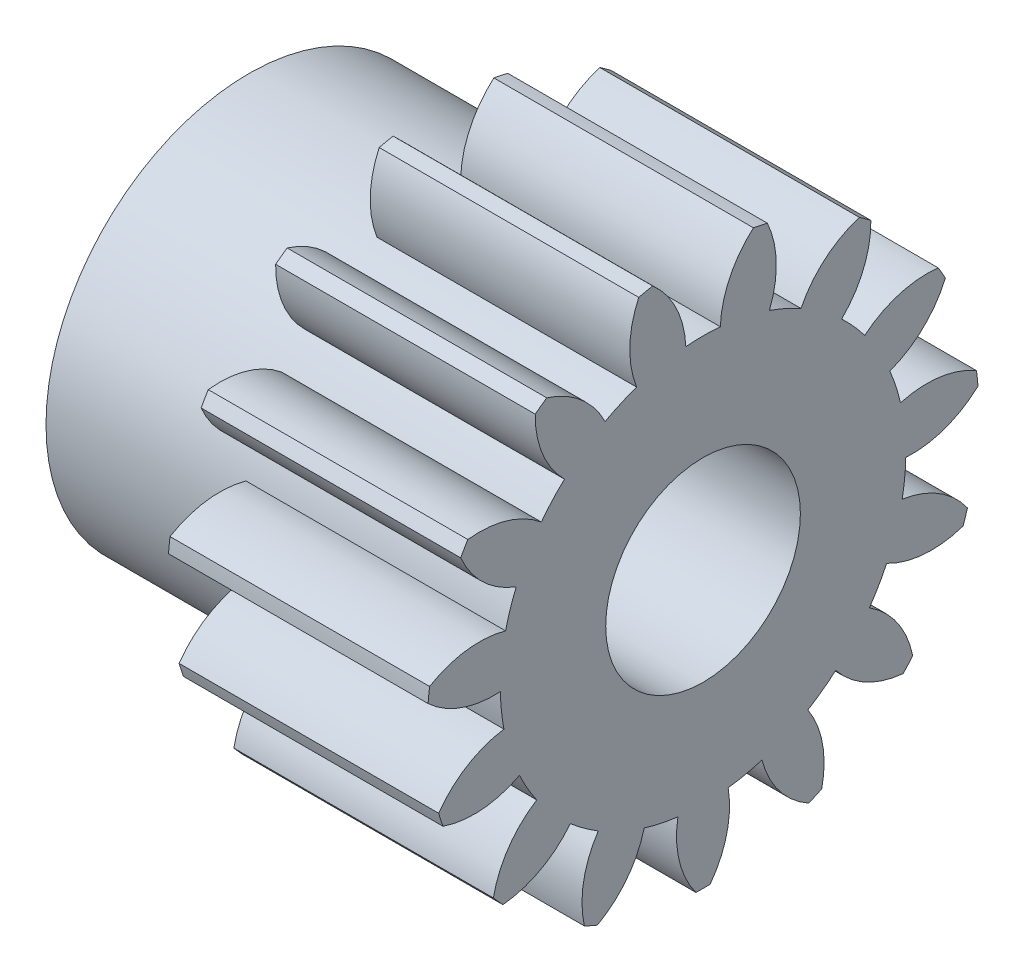
SolidWorks part; units mm, degrees
ref_plane "Plane1" through (0, 0, 0) normal (0, 0, 1) x (1, 0, 0)
ref_plane "Plane2" through (0, 0, 0) normal (0, 1, 0) x (1, 0, 0)
ref_plane "Plane3" through (0, 0, 0) normal (1, 0, 0) x (0, 0, -1)
sketch "HoldingSke" plane through (0, 0, 0) normal (0, 1, 0) x (1, 0, 0)
  line L0 (0, 0) -> (0.9659, -0.2588)
  line L1 (-15, 0) -> (100, 0) construction
  line L2 (0, 0) -> (-2.1039, 2.3779)
  line L3 (0, 0) -> (-11.863, 4.5341)
  line L4 (0, 0) -> (8.3417, 2.2352)
  line L5 (0, 0) -> (-10.3065, -3.844)
  line L6 (0, 0) -> (-6.6317, -4.4744)
  line L7 (-2.1039, 2.3779) -> (0.2639, 13.1202)
  line L8 (-76.2, 54.61) -> (-75.2, 54.61)
  line L9 (-71.009, 38.7566) -> (-53.1078, 45.2721)
  line L10 (-76.2, 71.12) -> (104.1128, 71.12)
  line L11 (0, 0) -> (-8, 0)
  line L12 (-76.2, 101.6) -> (-76.162, 101.6)
  line L13 (24.9733, 27.94) -> (52.9518, 28.4284)
  line L14 (24.9733, 27.94) -> (24.9743, 27.94)
  line L15 (24.9733, 27.94) -> (100.4006, 29.5858)
  line L16 (-63.627, -1) -> (-12.827, -1)
  circle A0 centre (0, 0) radius 3
  circle A1 centre (0, 0) radius 6.249
  circle A2 centre (0, 0) radius 6.5
  circle A3 centre (0, 0) radius 3
  dimension "Num_teeth" = 15
  dimension "Pitch_radius" = 180.3128
  dimension "Width" = 8
  dimension "Thickness" = 8
sketch "BasProSke" plane through (0, 0, 0) normal (0, 1, 0) x (1, 0, 0)
  line L0 (-10, 0) -> (60, 0) construction
  line L1 (0, 0) -> (0, 8.5)
  line L2 (0, 0) -> (8, 0)
  line L3 (8, 0) -> (8, 8.5)
  line L4 (8, 8.5) -> (0, 8.5)
  dimension "Thickness" = 8
  dimension "Diameter" = 17
revolve "Base-Revolve" add sketch "BasProSke" angle 360 about L0
sketch "TooCutSke" plane through (0, 0, 0) normal (1, 0, 0) x (0, 0, -1)
  line L1 (0, 0) -> (0, 107) construction
  line L2 (0, 0) -> (-0.8504, 7.4516) construction
  line L3 (0, 0) -> (-3.1044, 14.6049) construction
  line L4 (-0.8504, 7.4516) -> (-1.5522, 7.3025) construction
  arc A0 (0.5316, 6.2263) -> (-0.5316, 6.2263) centre (0, 0) ccw
  arc A1 (1.5766, 8.3784) -> (-1.5766, 8.3784) centre (0, 0) ccw
  circle A2 centre (0, 0) radius 7.5 construction
  circle A3 centre (0, 0) radius 7.0477 construction
  arc A4 (-0.5316, 6.2263) -> (-1.5766, 8.3784) centre (-3.5289, 6.1005) ccw
  arc A5 (1.5766, 8.3784) -> (0.5316, 6.2263) centre (3.5289, 6.1005) ccw
extrude "ToothCut" cut sketch "TooCutSke" along normal through all
fillet "Breaks" [suppressed] radius 0.02 tangent propagation no
fillet "RootFillets" [suppressed] radius 0.251
pattern_circular "TeethCuts" count 15 every 24 about axis through (-10, 0, 0) along (1, 0, 0) of "ToothCut", "RootFillets", "Breaks"
sketch "HubNeaOneSke" plane through (0, 0, 0) normal (-1, 0, 0) x (0, 0, 1)
  circle A0 centre (0, 0) radius 6.249
  dimension "Diameter" = 12.498
extrude "HubNearOne" add sketch "HubNeaOneSke" along normal blind 3.0002
ref_plane "FarPln" through (8, 0, 0) normal (1, 0, 0) x (0, 0, -1)
sketch "BorSke" plane through (0, 0, 0) normal (1, 0, 0) x (0, 0, -1)
  circle A0 centre (0, 0) radius 3
  dimension "Diameter" = 6
extrude "Bore" cut sketch "BorSke" along normal mid plane 22.0003
other "Move Face1" face at (-3.0002, 0, 3) offset 3 parameters "D1"=3
equation "' \"Module@HoldingSke\" = 6.35"
equation "' \"Num_teeth@HoldingSke\" = 12"
equation "' \"Ap@HoldingSke\" =  20"
equation "' \"Ap@HoldingSke\" = 20"
equation "' \"Width@HoldingSke\" = 0.5 * 25.4"
equation "' \"Hub_dia@HoldingSke\"= 1 * 25.4"
equation "' \"Hub_dia@HoldingSke\" = 1 * 25.4"
equation "' \"Overall_len@HoldingSke\" = 1.0 * 25.4"
equation "' \"Bore@HoldingSke\" = 0.75 * 25.4"
equation "' \"T_dim@HoldingSke\" = 0.1 * 25.4"
equation "' \"Width@KeySke\" = 0.25 * 25.4"
equation "' \"Show_teeth@HoldingSke\" = 13"
equation "' \"Backlash@HoldingSke\" = 0.009 * 25.4"
equation "' \"Addendum_fac@HoldingSke\" = 1.0"
equation "' \"Dedendum_fac@HoldingSke\" = 1.25"
equation "' \"Dedendum_add@HoldingSke\" = 0.00005 * 25.4"
equation "' \"Clearance_fac@HoldingSke\" = 0.25"
equation "\"Pitch@HoldingSke\" = 1 / \"Module@HoldingSke\""
equation "\"Overcut_dia@TooCutSke\" = (\"Num_teeth@HoldingSke\" + 2 * \"Addendum_fac@HoldingSke\") / \"Pitch@HoldingSke\" + 0.002 * 25.4"
equation "\"Pitch_dia@TooCutSke\" = \"Num_teeth@HoldingSke\" / \"Pitch@HoldingSke\""
equation "\"Base_dia@TooCutSke\" = \"Num_teeth@HoldingSke\" / \"Pitch@HoldingSke\" * cos((\"Ap@HoldingSke\"  * 3.14159265 / 180))"
equation "\"Root_dia@TooCutSke\" = (\"Num_teeth@HoldingSke\" + 2) / \"Pitch@HoldingSke\" - 2 * (\"Addendum_fac@HoldingSke\" + \"Dedendum_fac@HoldingSke\") / \"Pitch@HoldingSke\" - \"Dedendum_add@HoldingSke\" * 2"
equation "\"Half_ang@TooCutSke\" = 180 / \"Num_teeth@HoldingSke\""
equation "\"Half_CT@TooCutSke\" = \"Num_teeth@HoldingSke\" / \"Pitch@HoldingSke\" * sin((3.14159265 / 2 / \"Num_teeth@HoldingSke\")) / 2 - 7 * \"Backlash@HoldingSke\" / 4"
equation "\"Flank_rad@TooCutSke\" = \"Num_teeth@HoldingSke\" / \"Pitch@HoldingSke\" / 5"
equation "\"Radius@RootFillets\" = \"Clearance_fac@HoldingSke\" / \"Pitch@HoldingSke\" + \"Dedendum_add@HoldingSke\""
equation "\"Break_rad@Breaks\" = 0.02 / \"Pitch@HoldingSke\""
equation "\"Thickness@HoldingSke\" = \"Width@HoldingSke\""
equation "\"OAL@HoldingSke\" = \"Thickness@HoldingSke\""
equation "\"MHD@HoldingSke\" = (\"Num_teeth@HoldingSke\" + 2) / \"Pitch@HoldingSke\" - 2 * (\"Addendum_fac@HoldingSke\" + \"Dedendum_fac@HoldingSke\")  / \"Pitch@HoldingSke\" - \"Dedendum_add@HoldingSke\" * 2"
equation "\"MBD@HoldingSke\" = (\"Num_teeth@HoldingSke\" + 2) / \"Pitch@HoldingSke\" - 2 * (\"Addendum_fac@HoldingSke\" + \"Dedendum_fac@HoldingSke\")  / \"Pitch@HoldingSke\" - \"Dedendum_add@HoldingSke\" * 2 - 0.002 * 25.4"
equation "\"MHD@HoldingSke\" = ((sgn( \"MHD@HoldingSke\" - \"Hub_dia@HoldingSke\" )-1)*( \"MHD@HoldingSke\" - \"Hub_dia@HoldingSke\" ))/-2+ \"Hub_dia@HoldingSke\""
equation "\"MBD@HoldingSke\" = ((sgn( \"MBD@HoldingSke\" - \"Bore@HoldingSke\" )-1)*( \"MBD@HoldingSke\" - \"Bore@HoldingSke\" ))/-2+ \"Bore@HoldingSke\""
equation "\"OAL@HoldingSke\" = ((sgn( \"OAL@HoldingSke\" - \"Overall_len@HoldingSke\" )+1)*( \"OAL@HoldingSke\" - \"Overall_len@HoldingSke\" ))/2 + \"Overall_len@HoldingSke\" + 0.000002 * 25.4"
equation "\"Num_teeth@TeethCuts\" = int( \"Show_teeth@HoldingSke\" ) + 1"
equation "\"Num_teeth@TeethCuts\" = ((sgn( \"Num_teeth@TeethCuts\" - \"Num_teeth@HoldingSke\" )-1)*( \"Num_teeth@TeethCuts\" - \"Num_teeth@HoldingSke\" ))/-2+ \"Num_teeth@HoldingSke\""
equation "\"Num_teeth@TeethCuts\" = ((sgn( \"Num_teeth@TeethCuts\" - 2.0)+1)*( \"Num_teeth@TeethCuts\" - 2.0))/2 +2.0"
equation "\"Angle@TeethCuts\" = 360.0 / \"Num_teeth@HoldingSke\""
equation "\"Diameter@BasProSke\" = (\"Num_teeth@HoldingSke\" + 2 * \"Addendum_fac@HoldingSke\") / \"Pitch@HoldingSke\""
equation "\"Thickness@BasProSke\"  = \"Thickness@HoldingSke\""
equation "' \"Fillet_rad@BasProSke\" =  \"Thickness@HoldingSke\" * 0.05"
equation "' \"Fillet_rad@BasProSke\" = \"Thickness@HoldingSke\" * 0.05"
equation "\"MHD@HoldingSke\" = ((sgn( \"MHD@HoldingSke\" - \"Root_dia@TooCutSke\" )-1)*( \"MHD@HoldingSke\" - \"Root_dia@TooCutSke\" ))/-2+ \"Root_dia@TooCutSke\""
equation "\"Diameter@HubNeaOneSke\" = \"MHD@HoldingSke\""
equation "\"Length@HubNearOne\" = \"OAL@HoldingSke\" - \"Thickness@BasProSke\""
equation "\"Thickness@FarPln\" = \"Thickness@BasProSke\""
equation "\"Diameter@BorSke\" = \"MBD@HoldingSke\""
equation "\"D1@Bore\" = \"OAL@HoldingSke\" * 2.0"
